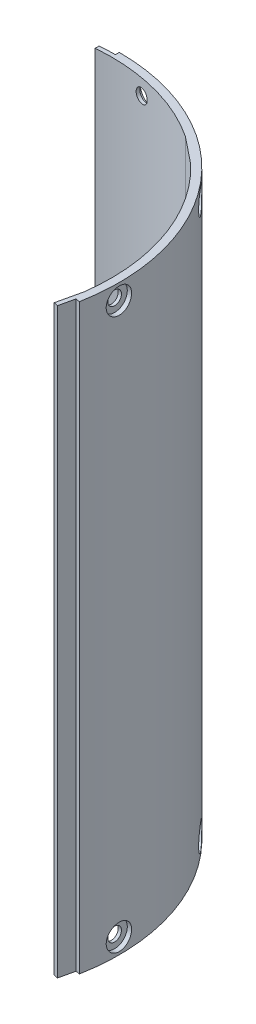
SolidWorks part; units mm, degrees
ref_plane "Спереди" through (0, 0, 0) normal (0, 0, 1) x (1, 0, 0)
ref_plane "Сверху" through (0, 0, 0) normal (0, 1, 0) x (1, 0, 0)
ref_plane "Справа" through (0, 0, 0) normal (1, 0, 0) x (0, 0, -1)
sketch "Эскиз2" plane through (0, 0, 0) normal (0, 1, 0) x (1, 0, 0)
  line L0 (0, -1000) -> (0, 49000) construction
  line L2 (33.9524, 35.3303) -> (27.0476, 40.8587) construction
  line L3 (48.5627, -6.5315) -> (46.5973, -15.1557) construction
  line L5 (33.9524, 35.3303) -> (27.0476, 40.8587)
  line L6 (48.5627, -6.5315) -> (46.5973, -15.1557) construction
  line L7 (-3.9968, 48.8367) -> (-3.9968, 49.84)
  line L10 (0, 50) -> (0, 49) construction
  line L12 (0, 0) -> (47.58, -10.8436) construction
  line L13 (50.1312, -9.3737) -> (49.0969, -9.138)
  line L14 (49.0969, -9.138) -> (48.2081, -13.038)
  line L15 (48.2081, -13.038) -> (47.1356, -12.7936)
  line L16 (47.58, -10.8436) -> (49.725, -11.3324) construction
  line L17 (47.1356, -12.7936) -> (48.5627, -6.5315)
  line L19 (0, 50) -> (0, 51)
  circle A0 centre (0, 0) radius 51 construction
  arc A1 (50.1312, -9.3737) -> (0, 51) centre (0, 0) ccw
  circle A2 centre (0, 0) radius 51 construction
  arc A3 (48.5627, -6.5315) -> (33.9524, 35.3303) centre (0, 0) ccw construction
  arc A4 (0, 51) -> (0, -51) centre (0, 0) ccw construction
  arc A5 (48.5627, -6.5315) -> (33.9524, 35.3303) centre (0, 0) ccw
  arc A6 (-3.9968, 48.8367) -> (27.0476, 40.8587) centre (0, 0) cw
  arc A7 (0, -51) -> (49.725, -11.3324) centre (0, 0) ccw construction
  arc A8 (49.725, -11.3324) -> (50.1312, -9.3737) centre (0, 0) ccw construction
  arc A9 (27.0476, 40.8587) -> (-27.0476, 40.8587) centre (0, 0) ccw construction
  arc A10 (0, 50) -> (-3.9968, 49.84) centre (0, 0) ccw
  point P25 (48.6525, -11.088)
  dimension "D1" = 3.9968
extrude "Бобышка-Вытянуть2" add sketch "Эскиз2" along normal up to surface (149 mm away)
ref_plane "Плоскость5" through (51, 0, 0) normal (1, 0, 0) x (0, 0, -1)
sketch "Эскиз15" plane through (51, 0, 0) normal (1, 0, 0) x (0, 0, -1)
  line L0 (0, -1000) -> (0, 49000) construction
  circle A0 centre (0, 4) radius 3.25
  dimension "D1" = 6.5
  dimension "D2" = 4
extrude "Вырез-Вытянуть5" cut sketch "Эскиз15" against normal blind 1.2
sketch "Эскиз16" plane through (49.8, 0, 0) normal (1, 0, 0) x (0, 0, -1)
  circle A0 centre (0, 4) radius 3.25 construction
  circle A1 centre (0, 4) radius 3.25 construction
  circle A2 centre (0, 4) radius 1.75
  dimension "D1" = 3.5
extrude "Вырез-Вытянуть6" cut sketch "Эскиз16" against normal through all
pattern_circular "Круговой массив3" count 5 every 20 about axis through (0, 0, 0) along (0, 1, 0) skipping 1, 3 of "Вырез-Вытянуть5", "Вырез-Вытянуть6"
sketch "Эскиз17" plane through (51, 0, 0) normal (1, 0, 0) x (0, 0, -1)
  line L0 (0, -1000) -> (0, 49000) construction
  line L1 (51, 149) -> (-9.3737, 149) construction
  circle A0 centre (0, 145) radius 3.25
  circle A1 centre (0, 4) radius 3.25 construction
  dimension "D1" = 4
extrude "Вырез-Вытянуть7" cut sketch "Эскиз17" against normal blind 1.2
sketch "Эскиз18" plane through (49.8, 0, 0) normal (1, 0, 0) x (0, 0, -1)
  circle A0 centre (0, 145) radius 3.25 construction
  circle A1 centre (0, 145) radius 3.25 construction
  circle A2 centre (0, 145) radius 1.75
  circle A3 centre (0, 4) radius 1.75 construction
extrude "Вырез-Вытянуть8" cut sketch "Эскиз18" against normal through all
pattern_circular "Круговой массив5" count 5 every 20 about axis through (0, 149, 0) along (0, 1, 0) skipping 1, 3 of "Вырез-Вытянуть8", "Вырез-Вытянуть7"
